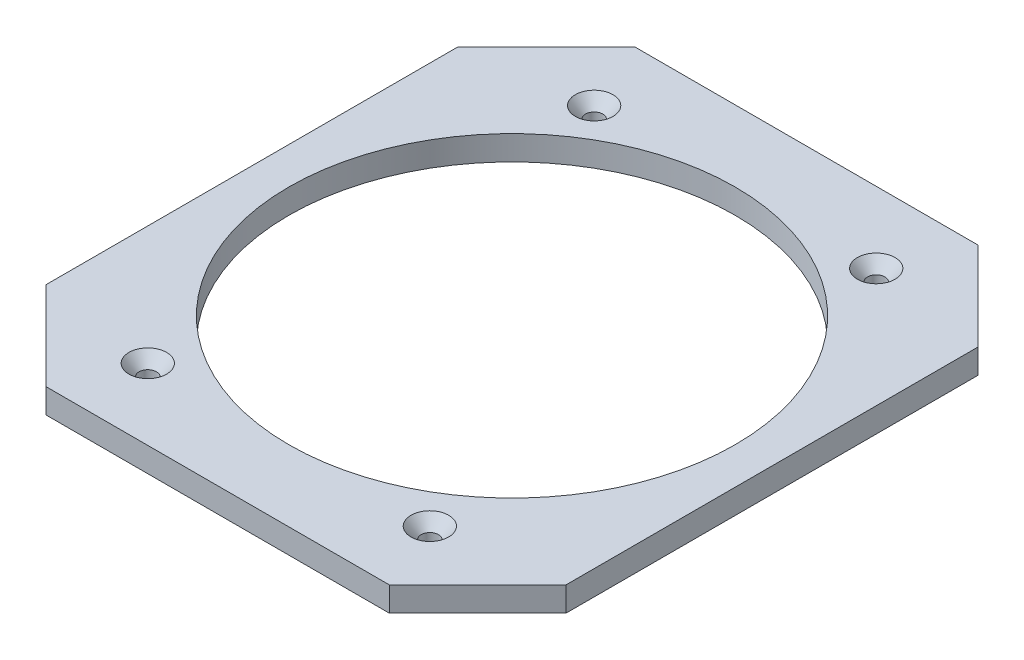
SolidWorks part; units mm, degrees
material "6061-T6 (SS)"
ref_plane "Front Plane" through (0, 0, 0) normal (0, 0, 1) x (1, 0, 0)
ref_plane "Top Plane" through (0, 0, 0) normal (0, 1, 0) x (1, 0, 0)
ref_plane "Right Plane" through (0, 0, 0) normal (1, 0, 0) x (0, 0, -1)
sketch "Sketch1" plane through (0, 0, 0) normal (0, 1, 0) x (1, 0, 0)
  line L0 (-67.31, 53.34) -> (-44.45, 76.2)
  line L1 (-44.45, -76.2) -> (44.45, -76.2)
  line L2 (-67.31, -53.34) -> (-67.31, 53.34)
  line L3 (-44.45, 76.2) -> (44.45, 76.2)
  line L4 (67.31, -53.34) -> (67.31, 53.34)
  line L5 (-85.725, -85.725) -> (85.725, 85.725) construction
  line L6 (-85.725, 85.725) -> (85.725, -85.725) construction
  line L7 (44.45, 76.2) -> (67.31, 53.34)
  line L8 (67.31, -53.34) -> (44.45, -76.2)
  line L9 (-67.31, -53.34) -> (-44.45, -76.2)
  circle A0 centre (0, 0) radius 54.61 construction
  point P0 (0, 0)
  point P16 (-67.31, 0)
  point P18 (0, 76.2)
  dimension "D4" = 109.22
  dimension "D1" = 171.45
  dimension "D2" = 171.45
  dimension "D3" = 88.9
  dimension "D5" = 152.4
  dimension "D6" = 12.7
extrude "Boss-Extrude1" add sketch "Sketch1" along normal blind 6.35
hole_wizard "CSK for #8 Flat Head Machine Screw1" positions "Sketch3" profile "Sketch2" countersink size "#8" standard "ANSI Inch" end condition through all
sketch "Sketch3" plane through (0, 6.35, 0) normal (0, 1, 0) x (-1, 0, 0)
  line L0 (-36.5125, -57.785) -> (0, 0) construction
  line L1 (0, 0) -> (36.5125, -57.785) construction
  line L5 (-1114.9397, -47.625) -> (48885.0603, -47.625) construction
  point P0 (36.5125, -57.785)
  point P1 (-36.5125, -57.785)
  dimension "D1" = 73.025
  dimension "D3" = 47.625
  dimension "D4" = 10.16
sketch "Sketch2" plane through (-36.5125, 6.35, -57.785) normal (1, 0, 0) x (0, 0, 1)
  line L0 (0, 0) -> (0, 6.35)
  line L1 (0, 6.35) -> (2.2479, 6.35)
  line L2 (2.2479, 6.35) -> (2.2479, 3.0265)
  line L3 (2.2479, 3.0265) -> (4.8788, 0)
  line L5 (4.8788, 0) -> (0, 0)
  line L6 (-2.2479, 3.0265) -> (-4.8788, 0) construction
  line L11 (0, -6.35) -> (0, 107.95) construction
  dimension "Thru Hole Dia." = 4.4958
  dimension "Thru Hole Depth" = 6.35
  dimension "Near C'Sink Dia." = 9.7576
  dimension "Near C'Sink Angle" = 82
ref_axis "Axis1" through (0, 0, 0) along (0, 1, 0)
pattern_circular "CirPattern1" count 2 over 360 about axis through (0, 0, 0) along (0, 1, 0) of "CSK for #8 Flat Head Machine Screw1"
sketch "Sketch4" plane through (0, 6.35, 0) normal (0, 1, 0) x (1, 0, 0)
  circle A0 centre (0, 0) radius 57.785
  dimension "D1" = 115.57
extrude "Cut-Extrude1" cut sketch "Sketch4" against normal through all
